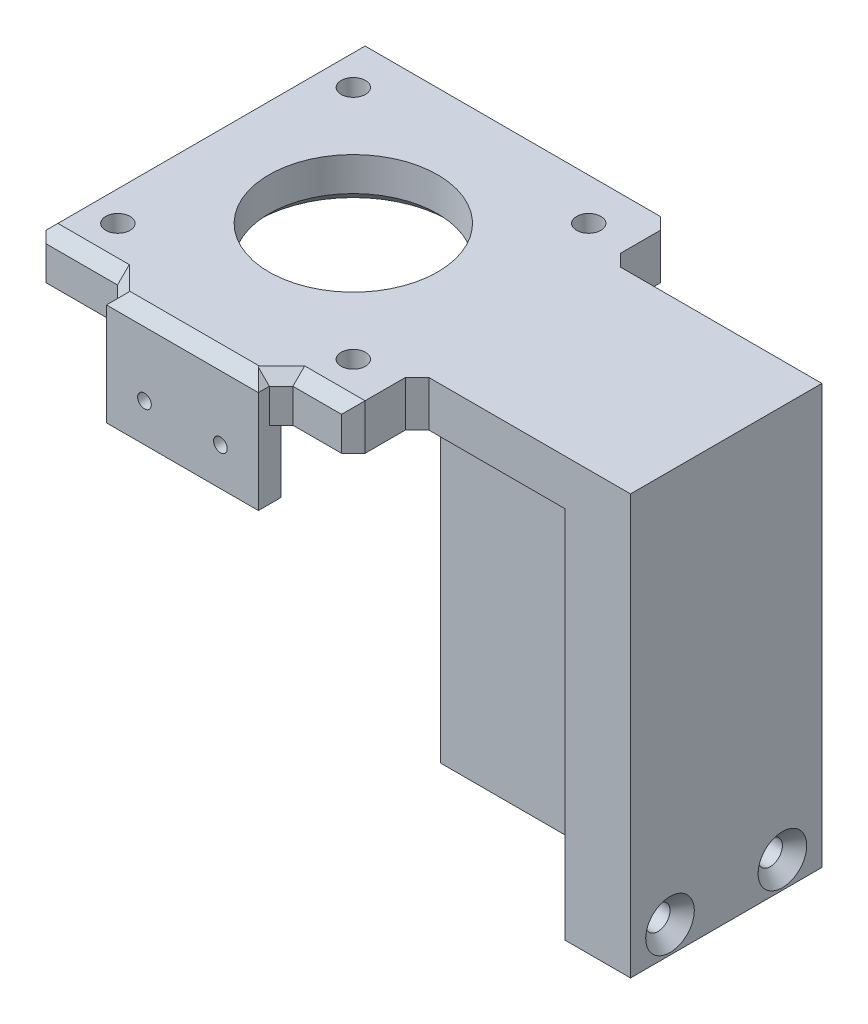
SolidWorks part; units mm, degrees
ref_plane "Front Plane" through (0, 0, 0) normal (0, 0, 1) x (1, 0, 0)
ref_plane "Top Plane" through (0, 0, 0) normal (0, 1, 0) x (1, 0, 0)
ref_plane "Right Plane" through (0, 0, 0) normal (1, 0, 0) x (0, 0, -1)
sketch "Sketch1" plane through (0, 0, 0) normal (0, 0, 1) x (1, 0, 0)
  line L0 (0, 0) -> (0, 11)
  line L1 (0, 11) -> (-19, 11)
  line L2 (0, 0) -> (8.8, 0)
  line L3 (8.8, 0) -> (8.8, 49.2)
  line L4 (8.8, 49.2) -> (-19, 49.2)
  line L5 (-19, 49.2) -> (-19, 11)
  dimension "D1" = 11
  dimension "D2" = 19
  dimension "D3" = 8.8
  dimension "D4" = 38.2
extrude "Boss-Extrude1" add sketch "Sketch1" along normal blind 25.2 contours L4 L5 L1 L0 L2 L3
sketch "Sketch2" plane through (0, 49.2, 0) normal (0, 1, 0) x (1, 0, 0)
  line L0 (8.8, -12.6) -> (-40.5, -12.6) construction
  line L2 (-40.5, 8.4) -> (-40.5, -33.6) construction
  line L3 (-61.5, 8.4) -> (-19.5, 8.4)
  line L4 (8.8, 0) -> (-19, 0)
  line L5 (-19, 0) -> (-19, -25.2)
  line L6 (-19, -25.2) -> (8.8, -25.2)
  line L7 (8.8, -25.2) -> (8.8, 0)
  line L8 (8.8, 0) -> (-19.5, 0)
  line L11 (8.8, -25.2) -> (8.8, 0)
  line L12 (-61.5, 8.4) -> (-61.5, -33.6)
  line L13 (-61.5, -33.6) -> (-19.5, -33.6)
  line L14 (-19.5, 8.4) -> (-19.5, 0)
  line L15 (-61.5, 8.4) -> (-19.5, -33.6) construction
  line L16 (-61.5, -33.6) -> (-19.5, 8.4) construction
  line L17 (-19.5, -25.2) -> (8.8, -25.2)
  line L18 (-19.5, -25.2) -> (-19.5, -33.6)
  circle A0 centre (-56, 2.9) radius 1.6
  circle A1 centre (-56, -28.1) radius 1.6
  circle A2 centre (-25, -28.1) radius 1.6
  circle A3 centre (-25, 2.9) radius 1.6
  dimension "D5" = 3.2
  dimension "D2" = 40.5
  dimension "D3" = 42
  dimension "D4" = 42
  dimension "D6" = 15.5
  dimension "D1" = 0
extrude "Boss-Extrude2" add sketch "Sketch2" along normal blind 6
sketch "Sketch3" plane through (0, 11, 0) normal (0, -1, 0) x (1, 0, 0)
  line L0 (-19, 24.2) -> (0, 24.2)
  line L1 (-19, 25.2) -> (0, 25.2)
  line L2 (-19, 25.2) -> (-19, 0)
  line L3 (-19, 0) -> (0, 0)
  line L4 (0, 25.2) -> (0, 0)
  line L5 (0, 1) -> (-19, 1)
  line M7 (-19, 0) -> (0, 0)
  line M8 (0, 0) -> (0, 25.2)
  line M9 (0, 25.2) -> (-19, 25.2)
  line M10 (-19, 25.2) -> (-19, 0)
  dimension "D1" = 1
  dimension "D2" = 1
extrude "Cut-Extrude1" cut sketch "Sketch3" against normal up to surface (38.2 mm away) contours L0 M10 M8 M9 | L5 L2 M8 M7 up to face at (-29.875, 49.2, 12.6)
chamfer "Chamfer2" distance 1.55 angle 45 4 edges at (-57.6, 49.2, -2.9) (-23.4, 49.2, -2.9) (-26.6, 49.2, 28.1) (-54.4, 49.2, 28.1)
sketch "Sketch4" plane through (0, 49.2, 0) normal (0, -1, 0) x (1, 0, 0)
  line L0 (-40.5, 33.6) -> (-40.5, -8.4) construction
  line L1 (-61.5, 33.6) -> (-19.5, 33.6) construction
  line L2 (-19.5, -8.4) -> (-61.5, -8.4) construction
  line L3 (-61.5, 12.6) -> (-40.5, 12.6) construction
  line L4 (-61.5, -8.4) -> (-61.5, 33.6) construction
  circle A0 centre (-40.5, 12.6) radius 11.1
  dimension "D1" = 22.2
extrude "Cut-Extrude2" cut sketch "Sketch4" against normal through all
chamfer "Chamfer3" distance 1.55 angle 45 11 edges at (-19, 30.1, 1) (-19, 30.1, 24.2) (-19.5, 52.2, 0) (-61.5, 52.2, -8.4) (-61.5, 55.2, 12.6) (-61.5, 52.2, 33.6) (-19.5, 52.2, -8.4) (-61.5, 49.2, 12.6) (-19.5, 52.2, 33.6) (-19.5, 52.2, 25.2) (-29.4, 49.2, 12.6)
chamfer "Chamfer4" distance 1 angle 45 2 edges at (0, 30.1, 24.2) (0, 30.1, 1)
sketch "Sketch5" plane through (8.8, 0, 0) normal (1, 0, 0) x (0, 0, -1)
  line L0 (-25.2, 0) -> (0, 0) construction
  line L1 (-12.6, 0) -> (-12.6, 55.2) construction
  line L3 (-25.2, 55.2) -> (0, 55.2) construction
  circle A0 centre (-12.6, 3.5) radius 1.6
  circle A1 centre (-5.2, 3.5) radius 1.6
  circle A2 centre (-20, 3.5) radius 1.6
  point P6 (0, 0)
  dimension "D1" = 3.2
  dimension "D2" = 3.5
  dimension "D3" = 2
extrude "Cut-Extrude3" cut sketch "Sketch5" against normal through all contours A2 | A1
sketch "Sketch6" plane through (0, 0, 33.6) normal (0, 0, 1) x (1, 0, 0)
  line L0 (-59.95, 55.2) -> (-21.05, 55.2) construction
  line L1 (-49, 55.2) -> (-29, 55.2)
  line L2 (-49, 55.2) -> (-49, 40.2)
  line L3 (-49, 40.2) -> (-29, 40.2)
  line L4 (-29, 55.2) -> (-29, 40.2)
  line L5 (-19, 11) -> (-19, 49.2) construction
  dimension "D1" = 10
  dimension "D2" = 20
  dimension "D3" = 15
extrude "Boss-Extrude3" add sketch "Sketch6" along normal blind 3
sketch "Sketch7" plane through (0, 0, 36.6) normal (0, 0, 1) x (1, 0, 0)
  line L0 (-39, 55.2) -> (-39, 40.2) construction
  line L1 (-29, 55.2) -> (-49, 55.2) construction
  line L2 (-49, 40.2) -> (-29, 40.2) construction
  line L3 (-49, 45.2) -> (-29, 45.2) construction
  line L4 (-49, 55.2) -> (-49, 40.2) construction
  line L5 (-29, 40.2) -> (-29, 55.2) construction
  circle A0 centre (-34, 45.2) radius 0.9
  circle A1 centre (-44, 45.2) radius 0.9
  dimension "D2" = 1.8
  dimension "D3" = 1.8
  dimension "D1" = 5
  dimension "D4" = 10
extrude "Cut-Extrude4" cut sketch "Sketch7" against normal through all
chamfer "Chamfer7" distance 1.55 angle 45 6 edges at (-29, 52.2, 33.6) (-25.025, 55.2, 33.6) (-29, 55.2, 35.1) (-49, 52.2, 33.6) (-49, 55.2, 35.1) (-54.475, 55.2, 33.6)
chamfer "Chamfer8" distance 1.55 angle 45 1 edges at (-39, 55.2, 36.6)
sketch "Sketch8" plane through (0, 0, 25.2) normal (0, 0, 1) x (1, 0, 0)
  line L0 (0, 0) -> (8.8, 0) construction
  line L1 (8.8, 55.2) -> (8.6, 55.2)
  line L2 (8.8, 55.2) -> (8.8, 0)
  line L3 (8.8, 0) -> (8.6, 0)
  line L4 (8.6, 55.2) -> (8.6, 0)
  dimension "D1" = 0.2
extrude "Cut-Extrude5" cut sketch "Sketch8" against normal through all
chamfer "Chamfer9" distance 1.6 angle 45 2 edges at (8.6, 1.9, 5.2) (8.6, 1.9, 20)
